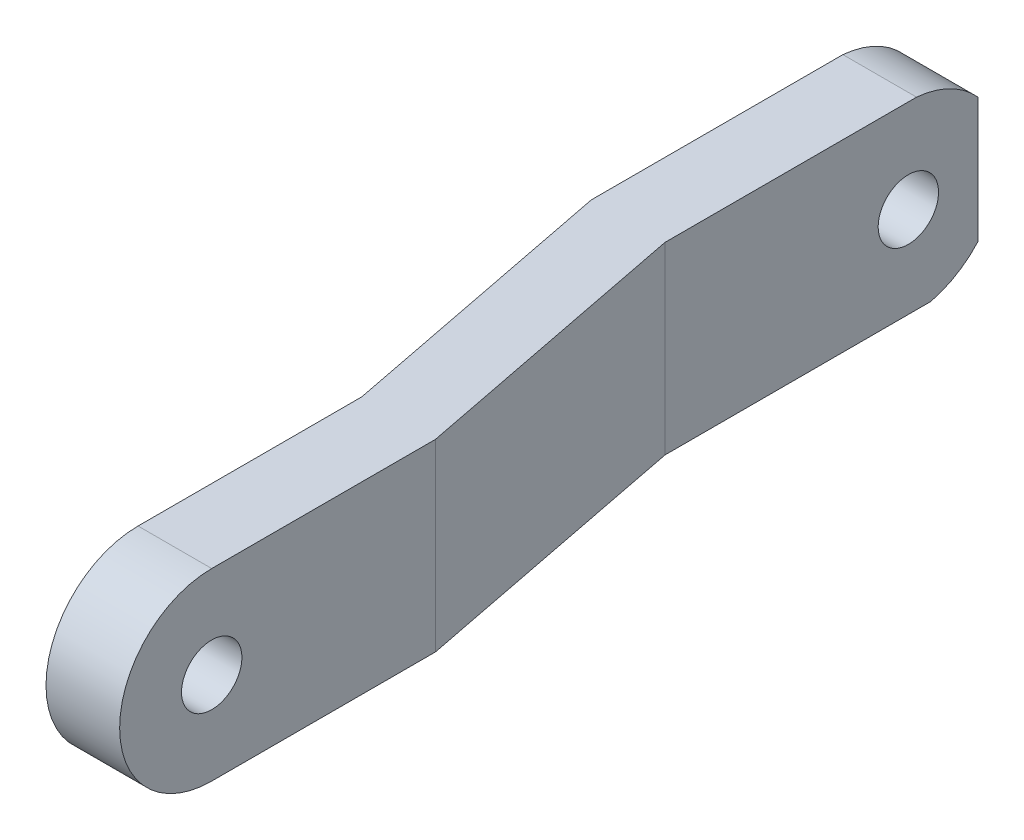
SolidWorks part; units mm, degrees
ref_plane "Front Plane" through (0, 0, 0) normal (0, 0, 1) x (1, 0, 0)
ref_plane "Top Plane" through (0, 0, 0) normal (0, 1, 0) x (1, 0, 0)
ref_plane "Right Plane" through (0, 0, 0) normal (1, 0, 0) x (0, 0, -1)
sketch "Sketch1" plane through (0, 0, 0) normal (0, 1, 0) x (1, 0, 0)
  line L2 (-21.4753, -26.1276) -> (-21.4753, -0.2067) construction
  line L15 (-24.0153, -26.2833) -> (-24.0153, -25.1794)
  line L19 (-21.4753, -28.3544) -> (-21.4753, -25.1794)
  line L20 (-21.4753, -20.6337) -> (-21.4753, -27.8908) construction
  line L21 (-21.4753, -28.3544) -> (-24.0153, -28.3544)
  line L22 (-24.0153, -28.3544) -> (-24.0153, -26.2833)
  line L24 (-21.4753, -25.1794) -> (-21.4753, -17.4603)
  line L26 (-24.0153, -25.1794) -> (-24.0153, -17.4603)
  line L32 (-23.4004, -7.62) -> (-21.4753, -17.4603)
  line L33 (-25.9404, -7.62) -> (-24.0153, -17.4603)
  line L35 (-25.9404, 3.175) -> (-23.4004, 3.175)
  line L37 (-25.9404, 3.175) -> (-25.9404, -7.62)
  line L38 (-23.4004, 3.175) -> (-23.4004, -7.62)
extrude "Boss-Extrude1" add sketch "Sketch1" along normal blind 6.35
sketch "Sketch3" plane through (-25.9404, 0, 0) normal (-1, 0, 0) x (0, 0, 1)
  line L4 (-3.175, 6.35) -> (7.62, 6.35) construction
  line L5 (0.2067, 0.3317) -> (0.8703, -5.3952) construction
  arc A2 (-0.4907, 6.35) -> (0, 0) centre (-0.7729, 3.1342) ccw
  circle A3 centre (-0.7729, 3.1342) radius 1.0414
  line M19 (-3.175, 0) -> (7.62, 0)
  line M21 (7.62, 6.35) -> (-3.175, 6.35)
  line M22 (-3.175, 6.35) -> (-3.175, 0)
extrude "Cut-Extrude1" cut sketch "Sketch3" against normal blind 3.556 and the other way through all contours A2 M21 M22 | A2 M22 M19 region at (-25.9404, 0.2922, -2.7036) region at (-25.9404, 6.0418, -2.6152)
sketch "Sketch4" plane through (-24.0153, 0, 0) normal (-1, 0, 0) x (0, 0, 1)
  line L0 (17.4603, 6.35) -> (28.3544, 6.35) construction
  line L1 (17.4603, 0) -> (28.3544, 0) construction
  arc A0 (25.1794, 6.35) -> (25.1794, 0) centre (25.1794, 3.175) cw
  circle A1 centre (25.1794, 3.175) radius 1.0414
  line M1 (17.4603, 0) -> (28.3544, 0)
  line M2 (28.3544, 0) -> (28.3544, 6.35)
  line M3 (28.3544, 6.35) -> (17.4603, 6.35)
extrude "Cut-Extrude2" cut sketch "Sketch4" against normal blind 3.556 and the other way through all contours A0 M3 M2 | A0 M2 M1 region at (-24.0153, 5.6408, 27.6452) region at (-24.0153, 0.7092, 27.6452)
extrude "Cut-Extrude3" cut sketch "Sketch4<3>" against normal blind 2.54 contours A1 region at (-24.0153, 3.175, 25.1794)
sketch "Sketch4<3>" plane through (-24.0153, 0, 0) normal (-1, 0, 0) x (0, 0, 1) same geometry as "Sketch4"
extrude "Cut-Extrude4" cut sketch "Sketch3<3>" against normal blind 2.54 contours A3 region at (-25.9404, 3.1342, -0.7729)
sketch "Sketch3<3>" plane through (-25.9404, 0, 0) normal (-1, 0, 0) x (0, 0, 1) same geometry as "Sketch3"
